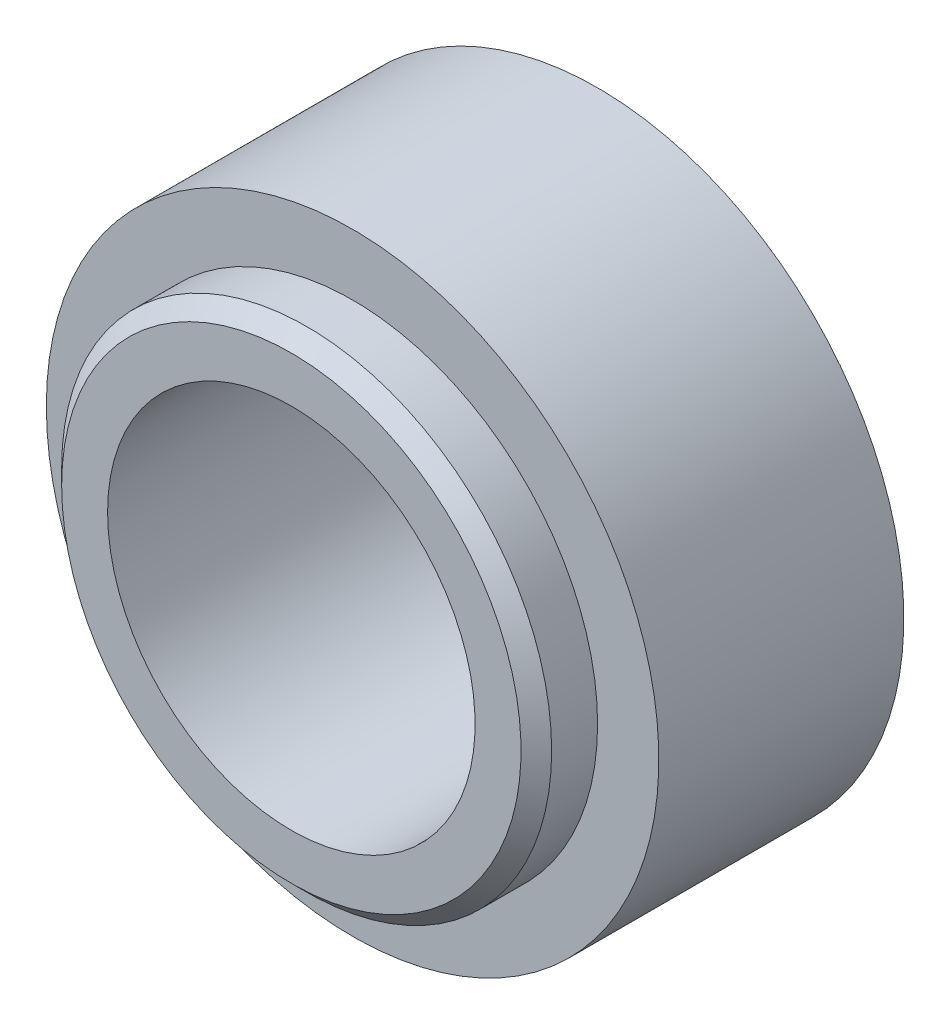
SolidWorks part; units mm, degrees
material "Tin Bearing Bronze"
ref_plane "Front Plane" through (0, 0, 0) normal (0, 0, 1) x (1, 0, 0)
ref_plane "Top Plane" through (0, 0, 0) normal (0, 1, 0) x (1, 0, 0)
ref_plane "Right Plane" through (0, 0, 0) normal (1, 0, 0) x (0, 0, -1)
sketch "Sketch1" plane through (0, 0, 0) normal (0, 0, 1) x (1, 0, 0)
  circle A0 centre (0, 0) radius 31.75
  circle A1 centre (0, 0) radius 25.4
  circle A2 centre (0, 0) radius 19.05
  dimension "D1" = 63.5
  dimension "D2" = 50.8
extrude "Boss-Extrude3" add sketch "Sketch1" along normal blind 25.4 contours A0 A1 region at (-30.852, 0, 0)
extrude "Boss-Extrude4" add sketch "Sketch1<3>" along normal blind 31.75 contours A1 A2 region at (-24.6816, 0, 0)
sketch "Sketch1<3>" plane through (0, 0, 0) normal (0, 0, 1) x (1, 0, 0) same geometry as "Sketch1"
chamfer "Chamfer1" distance 1.5875 angle 45 2 edges at (19.05, 0, 0) (25.4, 0, 31.75)
